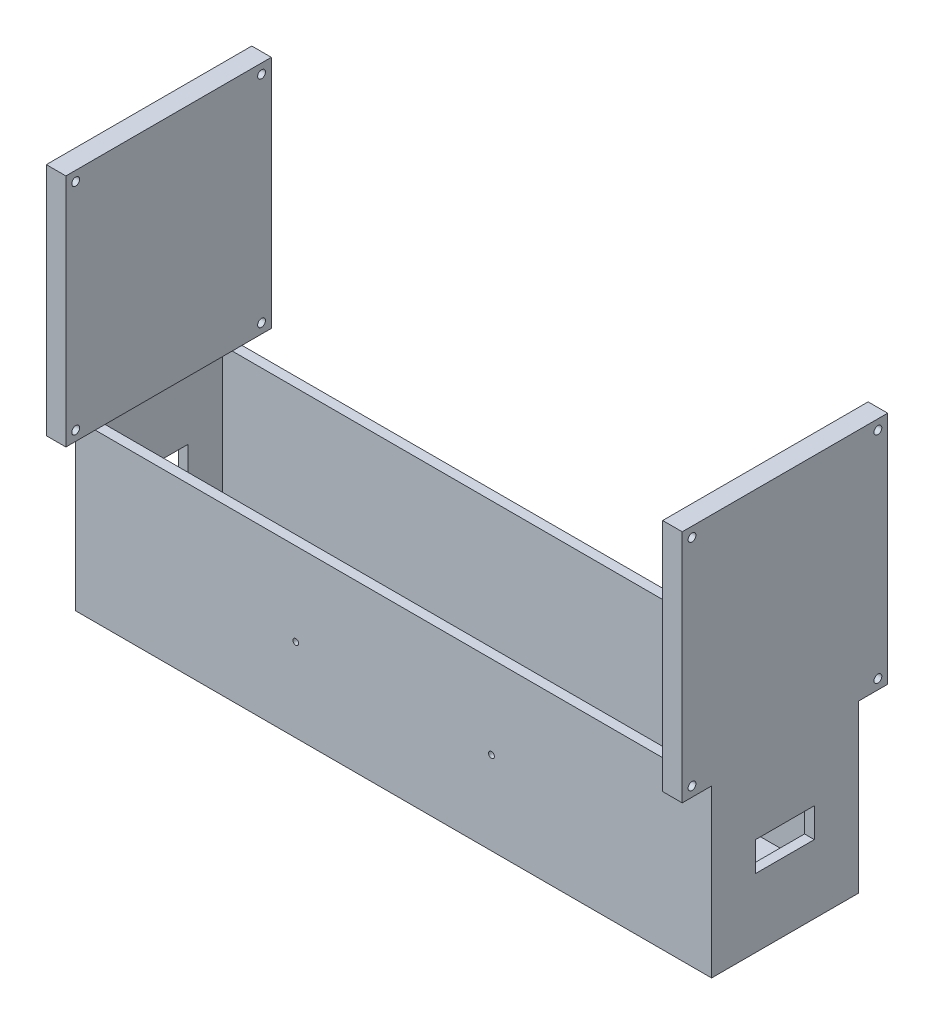
SolidWorks part; units mm, degrees
ref_plane "Front Plane" through (0, 0, 0) normal (0, 0, 1) x (1, 0, 0)
ref_plane "Top Plane" through (0, 0, 0) normal (0, 1, 0) x (1, 0, 0)
ref_plane "Right Plane" through (0, 0, 0) normal (1, 0, 0) x (0, 0, -1)
sketch "Sketch1" plane through (0, 0, 0) normal (0, 1, 0) x (1, 0, 0)
  line L1 (-162.5, -37.5) -> (162.5, -37.5)
  line L2 (-162.5, -37.5) -> (-162.5, 37.5)
  line L3 (-162.5, 37.5) -> (162.5, 37.5)
  line L4 (162.5, -37.5) -> (162.5, 37.5)
  line L5 (-162.5, -37.5) -> (162.5, 37.5) construction
  line L6 (-162.5, 37.5) -> (162.5, -37.5) construction
  point P0 (0, 0)
  dimension "D1" = 75
  dimension "D2" = 325
extrude "Boss-Extrude1" add sketch "Sketch1" along normal mid plane 85
sketch "Sketch2" plane through (0, 0, 37.5) normal (0, 0, 1) x (1, 0, 0)
  line L1 (0, -41.25) -> (0, 41.25) construction
  circle A0 centre (-50, 0) radius 1.5
  circle A1 centre (50, 0) radius 1.5
  dimension "D2" = 3
  dimension "D1" = 50
extrude "Cut-Extrude1" cut sketch "Sketch2" against normal blind 10
sketch "Sketch3" plane through (0, 42.5, 0) normal (0, 1, 0) x (1, 0, 0)
  line L1 (-162.5, -52.5) -> (-152.5, -52.5)
  line L2 (-162.5, -52.5) -> (-162.5, 52.5)
  line L3 (-162.5, 52.5) -> (-152.5, 52.5)
  line L4 (-152.5, -52.5) -> (-152.5, 52.5)
  line L5 (-152.5, 0) -> (-162.5, 0) construction
  line L6 (-46.75, 0) -> (46.75, 0) construction
  line L7 (-162.5, 37.5) -> (-162.5, -37.5) construction
  dimension "D1" = 10
  dimension "D2" = 105
extrude "Boss-Extrude2" add sketch "Sketch3" along normal blind 120
mirror "Mirror1" about plane through (0, 0, 0) normal (1, 0, 0) of "Boss-Extrude2"
shell "Shell1" thickness 5 removed face at (0, 42.5, 0)
sketch "Sketch4" plane through (162.5, 0, 0) normal (1, 0, 0) x (0, 0, -1)
  line L1 (-15, -7.5) -> (15, -7.5)
  line L2 (-15, -7.5) -> (-15, 7.5)
  line L3 (-15, 7.5) -> (15, 7.5)
  line L4 (15, -7.5) -> (15, 7.5)
  line L5 (-15, -7.5) -> (15, 7.5) construction
  line L6 (-15, 7.5) -> (15, -7.5) construction
  point P0 (0, 0)
  dimension "D1" = 15
  dimension "D2" = 30
extrude "Cut-Extrude2" cut sketch "Sketch4" against normal through all
sketch "Sketch5" plane through (162.5, 0, 0) normal (1, 0, 0) x (0, 0, -1)
  line L21 (47.5, 47.5) -> (37.5, 47.5)
  line L22 (-37.5, 47.5) -> (-47.5, 47.5)
  line L23 (47.5, 157.5) -> (47.5, 47.5)
  line L24 (-47.5, 157.5) -> (47.5, 157.5)
  line L25 (-47.5, 47.5) -> (-47.5, 157.5)
  line L26 (47.5, 47.5) -> (37.5, 47.5) construction
  line L27 (-37.5, 47.5) -> (-47.5, 47.5) construction
  line L28 (47.5, 157.5) -> (47.5, 47.5) construction
  line L29 (-47.5, 157.5) -> (47.5, 157.5) construction
  line L30 (-47.5, 47.5) -> (-47.5, 157.5) construction
  circle A0 centre (-47.5, 47.5) radius 2
  circle A1 centre (47.5, 47.5) radius 2
  circle A2 centre (47.5, 157.5) radius 2
  circle A3 centre (-47.5, 157.5) radius 2
  point P1 (0, 0)
  point P4 (46.3758, 47.5)
  point P7 (47.5, 155.6082)
  point P8 (-45.9097, 157.5)
  dimension "D1" = 5
extrude "Cut-Extrude3" cut sketch "Sketch5" against normal through all
